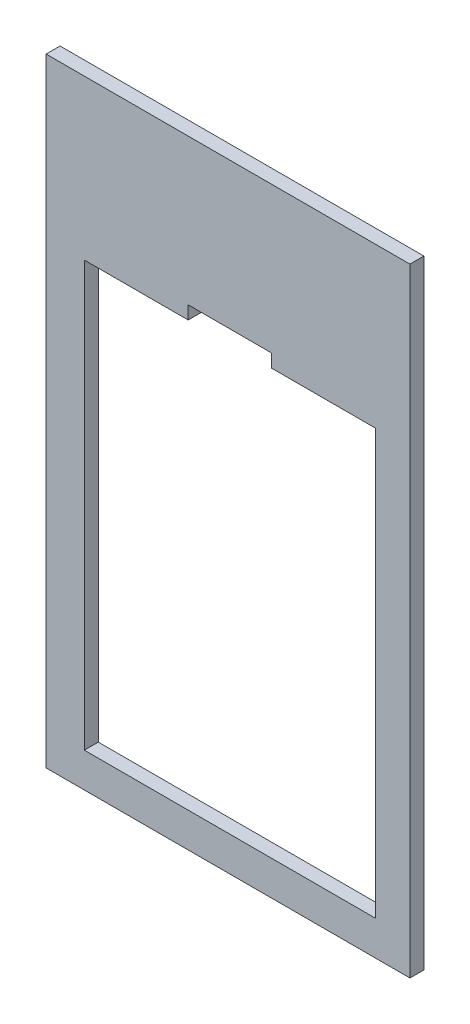
SolidWorks part; units mm, degrees
ref_plane "Front Plane" through (0, 0, 0) normal (0, 0, 1) x (1, 0, 0)
ref_plane "Top Plane" through (0, 0, 0) normal (0, 1, 0) x (1, 0, 0)
ref_plane "Right Plane" through (0, 0, 0) normal (1, 0, 0) x (0, 0, -1)
sketch "Sketch1" plane through (0, 0, 0) normal (0, 0, 1) x (1, 0, 0)
  line L0 (-41.465, 70.465) -> (-13.8217, 70.465)
  line L1 (-41.465, -70.465) -> (41.465, -70.465)
  line L2 (-41.465, -70.465) -> (-41.465, 70.465)
  line L3 (-41.465, 70.465) -> (41.465, 70.465) construction
  line L4 (41.465, -70.465) -> (41.465, 70.465)
  line L5 (-41.465, -70.465) -> (41.465, 70.465) construction
  line L6 (-41.465, 70.465) -> (41.465, -70.465) construction
  line L7 (-13.8217, 70.465) -> (13.8217, 70.465)
  line L8 (13.8217, 70.465) -> (41.465, 70.465)
  point P0 (0, 0)
  dimension "D1" = 82.93
  dimension "D2" = 140.93
extrude "Boss-Extrude1" add sketch "Sketch1" along normal blind 3.18
sketch "Sketch3" plane through (0, 0, 0) normal (0, 0, -1) x (-1, 0, 0)
  line L0 (-33.5967, 34.1533) -> (-33.5967, -62.5967)
  line L1 (-33.5967, -62.5967) -> (32.7533, -62.5967)
  line L2 (32.7533, -62.5967) -> (32.7533, 34.1533)
  line L3 (32.7533, 34.1533) -> (9.0783, 34.1533)
  line L4 (9.0783, 34.1533) -> (9.0783, 37.1533)
  line L5 (9.0783, 37.1533) -> (-9.9217, 37.1533)
  line L6 (-9.9217, 37.1533) -> (-9.9217, 34.1533)
  line L7 (-9.9217, 34.1533) -> (-33.5967, 34.1533)
  line L8 (32.7533, 43.1533) -> (-33.5967, 43.1533)
  line L9 (32.7533, -62.5967) -> (32.7533, 43.1533)
  line L10 (-33.5967, -62.5967) -> (32.7533, -62.5967)
  line L11 (-33.5967, 43.1533) -> (-33.5967, -62.5967)
  line L12 (-33.5967, -62.5967) -> (-33.5967, -70.465) construction
  line L13 (41.465, -70.465) -> (-41.465, -70.465) construction
  line L14 (-33.5967, -62.5967) -> (-41.465, -62.5967) construction
  line L15 (-41.465, -70.465) -> (-41.465, 70.465) construction
  dimension "D1" = 66.35
  dimension "D2" = 96.75
  dimension "D3" = 105.75
  dimension "D4" = 19
  dimension "D5" = 3
extrude "Cut-Extrude1" cut sketch "Sketch3" against normal through all contours L6 L7 L0 L1 L2 L3 L4 L5 region at (0.4217, -13.7828, 0)
